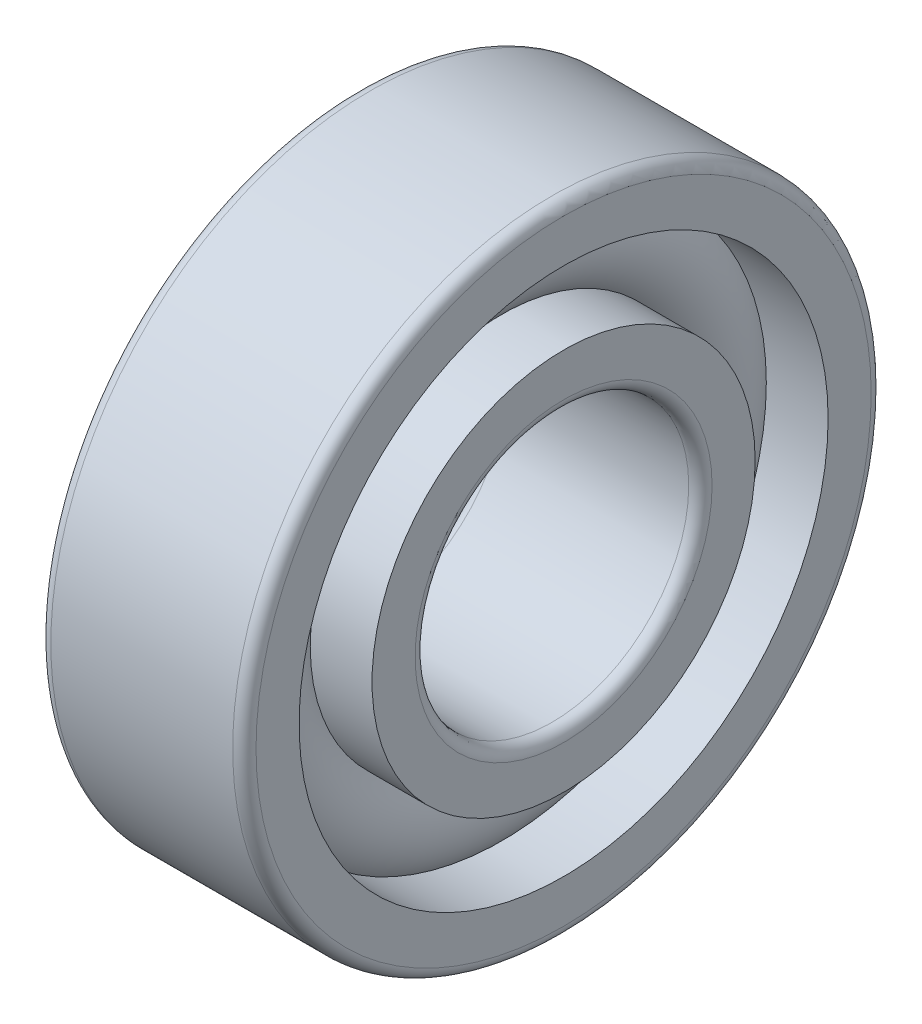
SolidWorks part; units mm, degrees
ref_plane "Plane1" through (0, 0, 0) normal (0, 0, 1) x (1, 0, 0)
ref_plane "Plane2" through (0, 0, 0) normal (0, 1, 0) x (1, 0, 0)
ref_plane "Plane3" through (0, 0, 0) normal (1, 0, 0) x (0, 0, -1)
sketch "Clipboard" plane through (0, 0, 0) normal (0, 0, 1) x (1, 0, 0)
  line L0 (-10, 0) -> (10, 0) construction
  line L1 (0, 0) -> (22.3471, -0.7804)
  line L2 (0, 0) -> (7.9327, 0.277)
  line L3 (0, 0) -> (22.3471, -0.7804)
  line L4 (0, 0) -> (-22.3573, -0.3902)
  dimension "BallCLRad" = 7.9375
sketch "CagSpiSke" plane through (0, 0, 0) normal (0, 0, 1) x (1, 0, 0)
  line L0 (0.1905, 7.62) -> (0.1905, 8.255)
  line L1 (0.1905, 8.255) -> (-0.1905, 8.255)
  line L2 (-0.1905, 8.255) -> (-0.1905, 7.62)
  line L3 (-0.1905, 7.62) -> (0.1905, 7.62)
  line L4 (-20.6375, 0) -> (20.6375, 0) construction
  line L5 (0, 0) -> (0, 23.7692) construction
  dimension "OD" = 16.51
  dimension "ID" = 15.24
revolve "CageSpine" add sketch "CagSpiSke" angle 0.001 about L4 reverse direction yes
ref_axis "Axis1" through (-50, 0, 0) along (1, 0, 0)
sketch "CagBalSke" plane through (0, 0, 0) normal (0, 0, 1) x (1, 0, 0)
  line L0 (-2.0955, 7.9375) -> (2.0955, 7.9375)
  line L1 (-1.905, 7.9375) -> (1.905, 7.9375) construction
  line L2 (-10, 0) -> (10, 0) construction
  line L3 (0, 0) -> (0, 24) construction
  arc A0 (2.0955, 7.9375) -> (-2.0955, 7.9375) centre (0, 7.9375) cw
  dimension "BallCLRad" = 7.9375
revolve "CageBall" [suppressed] add sketch "CagBalSke" angle 360 about L1 reverse direction yes
pattern_circular "CageBalls" [suppressed] count 2 every 180 about axis through (-50, 0, 0) along (1, 0, 0)
sketch "CagTrmODSke" plane through (0, 0, 0) normal (0, 0, 1) x (1, 0, 0)
  line L0 (2.1209, 8.255) -> (2.1209, 10.0584)
  line L1 (2.1209, 10.0584) -> (-2.1209, 10.0584)
  line L2 (-2.1209, 10.0584) -> (-2.1209, 8.255)
  line L3 (-2.1209, 8.255) -> (2.1209, 8.255)
  line L4 (-20.6375, 0) -> (20.6375, 0) construction
  line L5 (0, 0) -> (0, 25) construction
  dimension "Width" = 4.2418
  dimension "ID" = 16.51
  dimension "OD" = 20.1168
revolve "CageTrimOD" [suppressed] cut sketch "CagTrmODSke" angle 360 about L4 reverse direction yes
sketch "CagTrmIDSke" plane through (0, 0, 0) normal (0, 0, 1) x (1, 0, 0)
  line L0 (2.1209, 5.8674) -> (2.1209, 7.62)
  line L1 (2.1209, 7.62) -> (-2.1209, 7.62)
  line L2 (-2.1209, 7.62) -> (-2.1209, 5.8674)
  line L3 (-2.1209, 5.8674) -> (2.1209, 5.8674)
  line L4 (-20.6375, 0) -> (20.6375, 0) construction
  line L5 (0, 0) -> (0, 25) construction
  dimension "Width" = 4.2418
  dimension "ID" = 11.7348
  dimension "OD" = 15.24
revolve "CageTrimID" [suppressed] cut sketch "CagTrmIDSke" angle 360 about L4 reverse direction yes
sketch "BalSimSke" plane through (0, 0, 0) normal (0, 0, 1) x (1, 0, 0)
  line L0 (-10, 0) -> (10, 0) construction
  line L1 (-10, 7.9375) -> (10, 7.9375) construction
  line L2 (0, 0) -> (0, 23) construction
  circle A0 centre (0, 7.9375) radius 1.905
  dimension "BallCLRad" = 7.9375
  dimension "Ball_diameter" = 3.81
revolve "BallsSimplified" add sketch "BalSimSke" angle 360 about L0
sketch "BalDetSke" plane through (0, 0, 0) normal (0, 0, 1) x (1, 0, 0)
  line L0 (-1.905, 7.9375) -> (1.905, 7.9375)
  line L1 (-1.905, 7.9375) -> (1.905, 7.9375) construction
  line L2 (0, 0) -> (0, 25) construction
  arc A0 (1.905, 7.9375) -> (-1.905, 7.9375) centre (0, 7.9375) cw
  dimension "BallCLRad" = 7.9375
  dimension "Ball_diameter" = 3.81
revolve "BallDetailed" [suppressed] add sketch "BalDetSke" angle 360 about L1 reverse direction yes
sketch "InnRacSke" plane through (0, 0, 0) normal (0, 0, 1) x (1, 0, 0)
  line L0 (-1.3602, 6.6675) -> (-3.5712, 6.6675)
  line L1 (-3.5712, 6.6675) -> (-3.5712, 5.1689)
  line L2 (-3.1648, 4.7625) -> (3.1648, 4.7625)
  line L3 (3.5712, 5.1689) -> (3.5712, 6.6675)
  line L4 (3.5712, 6.6675) -> (1.411, 6.6675)
  line L5 (-20.6375, 0) -> (20.6375, 0) construction
  line L6 (0, 0) -> (0, 30) construction
  arc A0 (-3.5712, 5.1689) -> (-3.1648, 4.7625) centre (-3.1648, 5.1689) ccw
  arc A1 (3.1648, 4.7625) -> (3.5712, 5.1689) centre (3.1648, 5.1689) ccw
  arc A2 (1.411, 6.6675) -> (-1.3602, 6.6675) centre (0.0254, 7.9375) cw
  dimension "BallCLRad" = 7.9375
  dimension "Fillet_radius" = 0.4064
  dimension "Ball_diameter" = 3.7592
  dimension "ID" = 9.525
  dimension "OD" = 13.335
  dimension "Width" = 7.1425
revolve "InnerRace" add sketch "InnRacSke" angle 360 about L5 reverse direction yes
sketch "OutRacSke" plane through (0, 0, 0) normal (0, 0, 1) x (1, 0, 0)
  line L0 (-1.3856, 9.2075) -> (-3.5712, 9.2075)
  line L1 (-3.5712, 9.2075) -> (-3.5712, 10.7061)
  line L2 (-3.1648, 11.1125) -> (3.1648, 11.1125)
  line L3 (3.5712, 10.7061) -> (3.5712, 9.2075)
  line L4 (3.5712, 9.2075) -> (1.3856, 9.2075)
  line L5 (-20.6375, 0) -> (20.6375, 0) construction
  line L6 (0, 0) -> (0, 30) construction
  arc A0 (-3.5712, 10.7061) -> (-3.1648, 11.1125) centre (-3.1648, 10.7061) cw
  arc A1 (3.1648, 11.1125) -> (3.5712, 10.7061) centre (3.1648, 10.7061) cw
  arc A2 (1.3856, 9.2075) -> (-1.3856, 9.2075) centre (0, 7.9375) ccw
  dimension "BallCLRad" = 7.9375
  dimension "Fillet_radius" = 0.4064
  dimension "Ball_diameter" = 3.7592
  dimension "Width" = 7.1425
revolve "OuterRace" add sketch "OutRacSke" angle 360 about L5 reverse direction yes
pattern_circular "BallsDetailed" [suppressed] count 2 every 180 about axis through (-50, 0, 0) along (1, 0, 0)
equation "\"BallCLRad@Clipboard\" = ( \"OD@OutRacSke\" + \"ID@InnRacSke\" ) / 4"
equation "\"BallCLRad@BalSimSke\" = \"BallCLRad@Clipboard\""
equation "\"BallCLRad@BalDetSke\" = \"BallCLRad@Clipboard\""
equation "\"BallCLRad@InnRacSke\" = \"BallCLRad@Clipboard\""
equation "\"BallCLRad@OutRacSke\" = \"BallCLRad@Clipboard\""
equation "\"Ball_diameter@InnRacSke\" = \"Ball_diameter@BalDetSke\" - 0.002"
equation "\"Ball_diameter@OutRacSke\" = \"Ball_diameter@BalDetSke\" - 0.002"
equation "\"Ball_diameter@BalSimSke\" = \"Ball_diameter@BalDetSke\""
equation "\"Width@OutRacSke\" = \"Width@InnRacSke\""
equation "\"Fillet_radius@OutRacSke\" = \"Fillet_radius@InnRacSke\""
equation "\"Max_count@Clipboard\" = int( 3.14159265 / atn(( \"Ball_diameter@BalDetSke\" / 2) / sqr( \"BallCLRad@Clipboard\"  *  \"BallCLRad@Clipboard\" - ( \"Ball_diameter@BalDetSke\" / 2) *  ( \"Ball_diameter@BalDetSke\" / 2))))"
equation "\"Max_count@Clipboard\" = ((sgn( \"Max_count@Clipboard\" - \"Count@Clipboard\" )-1)*( \"Max_count@Clipboard\" - \"Count@Clipboard\" ))/-2+ \"Count@Clipboard\""
equation "\"Count@BallsDetailed\" = int( \"Show_count@Clipboard\" ) "
equation "\"Count@BallsDetailed\" = ((sgn( \"Count@BallsDetailed\" - \"Max_count@Clipboard\" )-1)*( \"Count@BallsDetailed\" - \"Max_count@Clipboard\" ))/-2+ \"Max_count@Clipboard\""
equation "\"Count@BallsDetailed\" = ((sgn( \"Count@BallsDetailed\" - \"Min_count@Clipboard\" )+1)*( \"Count@BallsDetailed\" - \"Min_count@Clipboard\"))/2 +\"Min_count@Clipboard\""
equation "\"Angle@BallsDetailed\" = 360.0 / \"Max_count@Clipboard\""
equation "\"BallCLRad@CagBalSke\" = \"BallCLRad@Clipboard\""
equation "\"Count@CageBalls\" = \"Count@BallsDetailed\""
equation "\"Angle@CageBalls\" = \"Angle@BallsDetailed\""
equation "\"Angle@CageSpine\" =  \"Angle@CageBalls\" * ( \"Count@CageBalls\" -1 + int( \"Count@CageBalls\" / \"Max_count@Clipboard\" ) )  + 0.001 -  int( \"Count@CageBalls\" / \"Max_count@Clipboard\" ) * 0.001"
equation "\"Angle@CageSpine\" =  \"Angle@CageSpine\" * int( \"Min_count@Clipboard\" / 2) + int(1 / \"Min_count@Clipboard\")  * 0.001"
equation "\"CageWallOD@CagBalSke\" =  \"Ball_diameter@BalDetSke\" * 1.1"
equation "\"Thickness@CagSpiSke\" =  \"Ball_diameter@BalDetSke\" * 0.1"
equation "\"OD@CagTrmODSke\" = \"BallCLRad@Clipboard\" * 2 + \"CageWallOD@CagBalSke\" + 0.002"
equation "\"ID@CagTrmODSke\" = \"BallCLRad@Clipboard\" * 2 + \"Ball_diameter@BalDetSke\" / 6"
equation "\"OD@CagTrmIDSke\" = \"BallCLRad@Clipboard\" * 2 - \"Ball_diameter@BalDetSke\" / 6"
equation "\"ID@CagTrmIDSke\" = \"BallCLRad@Clipboard\" * 2 - \"CageWallOD@CagBalSke\" + 0.002"
equation "\"OD@CagSpiSke\" = \"ID@CagTrmODSke\""
equation "\"ID@CagSpiSke\" = \"OD@CagTrmIDSke\""
equation "\"Width@CagTrmODSke\" = \"CageWallOD@CagBalSke\" + 0.002"
equation "\"Width@CagTrmIDSke\" = \"CageWallOD@CagBalSke\" + 0.002"
